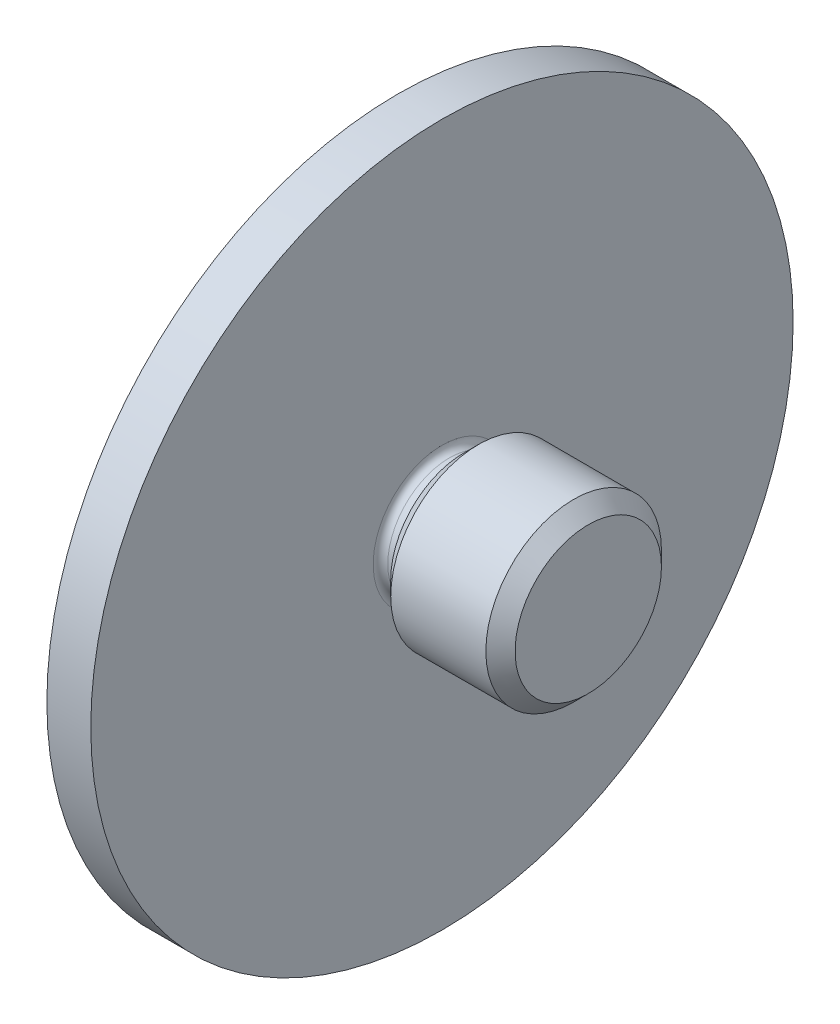
SolidWorks part; units mm, degrees
ref_plane "Спереди" through (0, 0, 0) normal (0, 0, 1) x (1, 0, 0)
ref_plane "Сверху" through (0, 0, 0) normal (0, 1, 0) x (1, 0, 0)
ref_plane "Справа" through (0, 0, 0) normal (1, 0, 0) x (0, 0, -1)
sketch "Эскиз1" plane through (0, 0, 0) normal (1, 0, 0) x (0, 0, -1)
  circle A0 centre (0, 0) radius 24
  dimension "D1" = 48
extrude "Бобышка-Вытянуть1" add sketch "Эскиз1" along normal blind 3
sketch "Эскиз2" plane through (3, 0, 0) normal (1, 0, 0) x (0, 0, -1)
  circle A0 centre (0, 0) radius 6
  dimension "D1" = 12
extrude "Бобышка-Вытянуть2" add sketch "Эскиз2" along normal blind 10
sketch "Эскиз3" plane through (0, 0, 0) normal (0, 0, 1) x (1, 0, 0)
  line L0 (0, 0) -> (14.9328, 0) construction
  line L1 (3, 6) -> (3, 4.2)
  line L2 (3, 4.2) -> (4.5, 4.2)
  line L3 (4.5, 4.2) -> (4.5, 6)
  line L4 (13, 6) -> (3, 6) construction
  line L5 (4.5, 6) -> (3, 6)
  point P6 (4.2078, 6)
  dimension "D1" = 1.5
  dimension "D2" = 1.8
revolve "Вырез-Повернуть1" cut sketch "Эскиз3" angle 360 about L0
fillet "Скругление1" radius 0.5 2 edges at (3, 0, 4.2) (4.5, 0, 4.2)
chamfer "Фаска1" distance 1 angle 45 2 edges at (13, 0, -6) (4.5, 0, 6)
sketch "Эскиз4" plane through (0, 0, 0) normal (-1, 0, 0) x (0, 0, 1)
  circle A0 centre (0, 0) radius 5
  dimension "D1" = 10
extrude "Бобышка-Вытянуть3" add sketch "Эскиз4" along normal blind 0.5
fillet "Скругление2" radius 0.5 1 edges at (0, 0, 5)
sketch "Эскиз5" plane through (-0.5, 0, 0) normal (-1, 0, 0) x (0, 0, 1)
  circle A0 centre (0, 0) radius 4
  dimension "D1" = 8
extrude "Бобышка-Вытянуть4" add sketch "Эскиз5" along normal blind 8
hole_wizard "Отверстие обработанное метчиком M31" positions "Эскиз6" profile "Эскиз7" tap size "M3" standard "ISO"
sketch "Эскиз6" plane through (-8.5, 0, 0) normal (-1, 0, 0) x (0, 0, 1)
  point P0 (0, 0)
sketch "Эскиз7" plane through (-8.5, 0, 0) normal (0, 1, 0) x (0, 0, 1)
  line L0 (0, 0) -> (0, 9.2511)
  line L1 (0, 9.2511) -> (1.25, 8.5)
  line L2 (1.25, 8.5) -> (1.25, 1.25)
  line L3 (1.25, 1.25) -> (2.5, 0)
  line L5 (2.5, 0) -> (0, 0)
  line L6 (-1.25, 1.25) -> (-2.5, 0) construction
  line L10 (0, 9.2511) -> (-1.25, 8.5) construction
  line L11 (0, -6.35) -> (0, 107.95) construction
  dimension "Диаметр сверла" = 2.5
  dimension "Глубина сверла" = 8.5
  dimension "Диаметр передней зенковки" = 5
  dimension "Угол передней зенковки" = 90
  dimension "Угол заточки сверла" = 118
